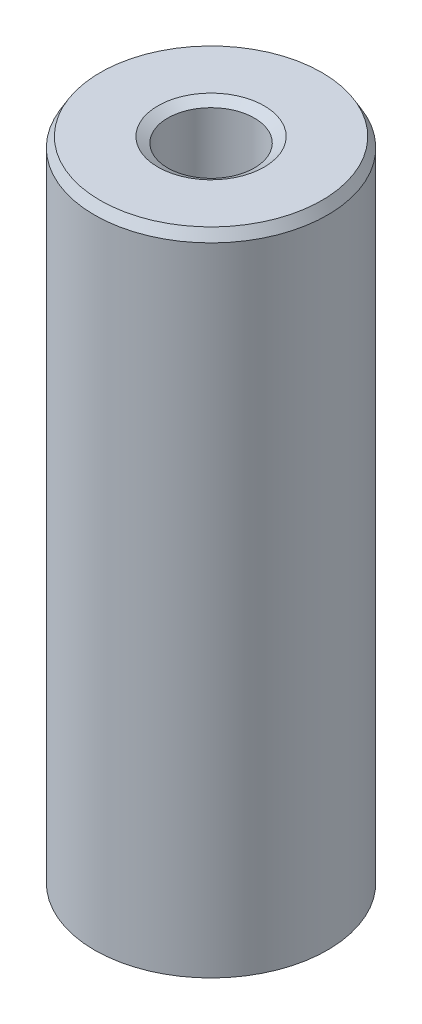
SolidWorks part; units mm, degrees
ref_plane "Front Plane" through (0, 0, 0) normal (0, 0, 1) x (1, 0, 0)
ref_plane "Top Plane" through (0, 0, 0) normal (0, 1, 0) x (1, 0, 0)
ref_plane "Right Plane" through (0, 0, 0) normal (1, 0, 0) x (0, 0, -1)
sketch "Sketch1" plane through (0, 0, 0) normal (0, 1, 0) x (1, 0, 0)
  circle A0 centre (0, 0) radius 22.5
  dimension "SLEEVE_OD" = 45
extrude "Boss-Extrude1" add sketch "Sketch1" along normal blind 125.9427
sketch "Sketch2" plane through (0, 0, 0) normal (0, 1, 0) x (1, 0, 0)
  circle A0 centre (0, 0) radius 8.3643
  dimension "BORE_D" = 16.7285
extrude "Cut-Extrude1" cut sketch "Sketch2" along normal through all
chamfer "Chamfer1" distance 1.8989 angle 30 4 edges at (0, 125.9427, 8.3643) (0, 0, 8.3643) (0, 0, 22.5) (0, 125.9427, 22.5) first distance on face at (0, 125.9427, 8.3643) first distance on face at (0, 0, 8.3643) first distance on face at (0, 125.9427, 22.5)
